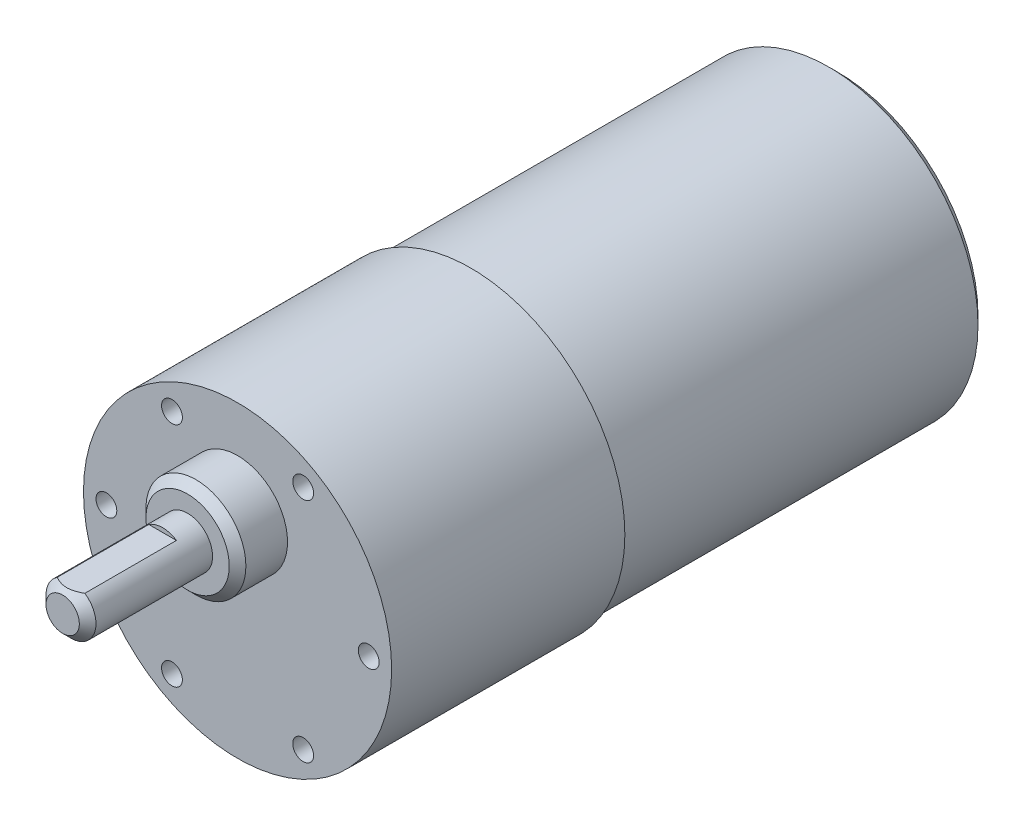
SolidWorks part; units mm, degrees
ref_plane "正面" through (0, 0, 0) normal (0, 0, 1) x (1, 0, 0)
ref_plane "平面" through (0, 0, 0) normal (0, 1, 0) x (1, 0, 0)
ref_plane "右側面" through (0, 0, 0) normal (1, 0, 0) x (0, 0, -1)
sketch "ｽｹｯﾁ1" plane through (0, 0, 0) normal (0, 0, 1) x (1, 0, 0)
  circle A0 centre (0, 0) radius 17.9
  dimension "D1" = 35.8
extrude "ﾎﾞｽ - 押し出し1" add sketch "ｽｹｯﾁ1" along normal blind 44
sketch "ｽｹｯﾁ2" plane through (0, 0, 44) normal (0, 0, 1) x (1, 0, 0)
  circle A0 centre (0, 0) radius 18.5
  dimension "D1" = 37
extrude "ﾎﾞｽ - 押し出し2" add sketch "ｽｹｯﾁ2" along normal blind 28
sketch "ｽｹｯﾁ3" plane through (0, 0, 72) normal (0, 0, 1) x (1, 0, 0)
  line L0 (0, 0) -> (0, 7)
  circle A0 centre (0, 7) radius 6
  dimension "D2" = 12
  dimension "D1" = 7
extrude "ﾎﾞｽ - 押し出し3" add sketch "ｽｹｯﾁ3" along normal blind 6 contours A0 region at (4.1226, 2.8774, 72)
sketch "ｽｹｯﾁ4" plane through (0, 0, 78) normal (0, 0, 1) x (1, 0, 0)
  circle A0 centre (0, 7) radius 3
  dimension "D1" = 6
extrude "ﾎﾞｽ - 押し出し4" add sketch "ｽｹｯﾁ4" along normal blind 15
sketch "ｽｹｯﾁ5" plane through (0, 0, 93) normal (0, 0, 1) x (1, 0, 0)
  line L0 (0, 7) -> (0, 9.5)
  line L2 (-2.0662, 9.5) -> (2.6383, 9.5)
  line L3 (-2.0662, 9.5) -> (-2.0662, 10.42)
  line L4 (-2.0662, 10.42) -> (2.6383, 10.42)
  line L5 (2.6383, 9.5) -> (2.6383, 10.42)
  circle M2 centre (0, 7) radius 3
  dimension "D1" = 2.5
extrude "ｶｯﾄ - 押し出し1" cut sketch "ｽｹｯﾁ5" against normal blind 12 contours L2 M2 region at (0, 9.7015, 93)
sketch "ｽｹｯﾁ6" plane through (0, 0, 72) normal (0, 0, 1) x (1, 0, 0)
  line L0 (0, 0) -> (0, 15.75)
  line L1 (0, 0) -> (7.875, 13.6399)
  line L2 (0, 0) -> (15.75, 0)
  line L3 (0, 0) -> (7.875, -13.6399)
  line L4 (0, 0) -> (-7.875, -13.6399)
  line L5 (0, 0) -> (-15.75, 0)
  line L6 (0, 0) -> (-7.875, 13.6399)
  circle A0 centre (-7.875, 13.6399) radius 2.141
  circle A1 centre (-15.75, 0) radius 2.1519
  circle A2 centre (-7.875, -13.6399) radius 1.7453
  circle A3 centre (7.875, -13.6399) radius 1.7498
  circle A4 centre (15.75, 0) radius 1.9314
  circle A5 centre (7.875, 13.6399) radius 1.9477
  dimension "D1" = 15.75
  dimension "D2" = 15.75
  dimension "D3" = 30
  dimension "D4" = 60
  dimension "D5" = 60
  dimension "D6" = 15.75
  dimension "D7" = 15.75
  dimension "D8" = 60
  dimension "D9" = 60
  dimension "D10" = 60
  dimension "D11" = 15.75
  dimension "D12" = 15.75
  dimension "D13" = 15.75
hole_wizard "M3x0.5 ねじ穴1" positions "3Dｽｹｯﾁ1" profile "ｽｹｯﾁ7" tap size "M3x0.5" standard "JIS"
sketch3d "3Dｽｹｯﾁ1"
  point P0 (-15.75, 0, 72)
  point P3 (-7.875, -13.6399, 72)
  point P6 (7.875, -13.6399, 72)
  point P9 (15.75, 0, 72)
  point P12 (7.875, 13.6399, 72)
  point P15 (-7.875, 13.6399, 72)
sketch "ｽｹｯﾁ7" plane through (-15.75, 0, 72) normal (1, 0, 0) x (0, -1, 0)
  line L0 (0, 0) -> (0, 9.2511)
  line L1 (0, 9.2511) -> (1.25, 8.5)
  line L2 (1.25, 8.5) -> (1.25, 0)
  line L5 (1.25, 0) -> (0, 0)
  line L10 (0, 9.2511) -> (-1.25, 8.5) construction
  line L11 (0, -6.35) -> (0, 107.95) construction
  dimension "ねじ下穴ﾄﾞﾘﾙ直径" = 2.5
  dimension "ねじ下穴ﾄﾞﾘﾙの深さ" = 8.5
  dimension "ﾄﾞﾘﾙ角度" = 118
cosmetic thread "穴のねじ山1" parameters "D1"=6, "D2"=3
cosmetic thread "穴のねじ山2" parameters "D1"=6, "D2"=3
cosmetic thread "穴のねじ山3" parameters "D1"=6, "D2"=3
cosmetic thread "穴のねじ山4" parameters "D1"=6, "D2"=3
cosmetic thread "穴のねじ山5" parameters "D1"=6, "D2"=3
cosmetic thread "穴のねじ山6" parameters "D1"=6, "D2"=3
chamfer "面取り1" distance 1 angle 45 1 edges at (0, 4, 93)
chamfer "面取り2" distance 1 angle 45 1 edges at (6, 7, 78)
chamfer "面取り3" distance 1 angle 45 1 edges at (17.9, 0, 0)
